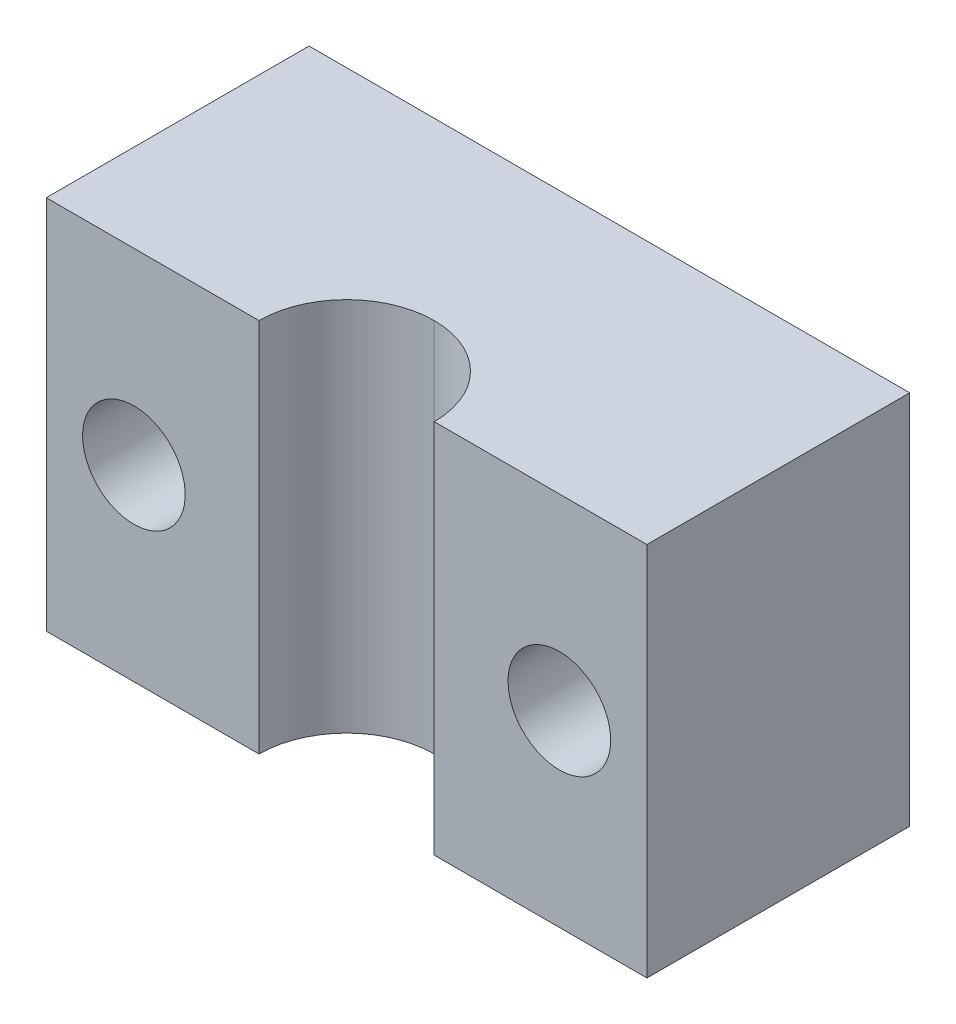
SolidWorks part; units mm, degrees
ref_plane "Спереди" through (0, 0, 0) normal (0, 0, 1) x (1, 0, 0)
ref_plane "Сверху" through (0, 0, 0) normal (0, 1, 0) x (1, 0, 0)
ref_plane "Справа" through (0, 0, 0) normal (1, 0, 0) x (0, 0, -1)
sketch "Эскиз1" plane through (0, 0, 0) normal (0, 1, 0) x (1, 0, 0)
  line L1 (-24, -10) -> (24, -10)
  line L2 (-24, -10) -> (-24, 10)
  line L3 (-24, 10) -> (24, 10)
  line L4 (24, -10) -> (24, 10)
  line L5 (-24, -10) -> (24, 10) construction
  line L6 (-24, 10) -> (24, -10) construction
  point P0 (0, 0)
  dimension "D1" = 48
  dimension "D2" = 20
extrude "Бобышка-Вытянуть1" add sketch "Эскиз1" along normal blind 30
sketch "Эскиз2" plane through (0, 0, 10) normal (0, 0, 1) x (1, 0, 0)
  line L0 (-7, 30) -> (-7, 0)
  line L1 (-24, 30) -> (24, 30) construction
  line L2 (-24, 0) -> (24, 0) construction
  line L3 (-7, 0) -> (7, 0)
  line L4 (7, 0) -> (7, 30)
  line L5 (7, 30) -> (-7, 30)
  dimension "D1" = 17
  dimension "D2" = 14
extrude "Вырез-Вытянуть1" cut sketch "Эскиз2" against normal blind 7
sketch "Эскиз7" plane through (24, 0, 0) normal (1, 0, 0) x (0, 0, -1)
  line L1 (32, 30) -> (32, 0)
  line L2 (32, 0) -> (10, 0)
  line L3 (-10, 0) -> (10, 0)
  line L4 (10, 0) -> (10.066, 0.2736)
  line L5 (10, 30) -> (32, 30)
  line L8 (10, 0) -> (10, 30)
  dimension "D3" = 22
extrude "Бобышка-Вытянуть2" add sketch "Эскиз7" against normal blind 48
sketch "Эскиз8" plane through (24, 0, 0) normal (1, 0, 0) x (0, 0, -1)
  line L0 (11, 0) -> (11, 30)
  line L1 (-10, 30) -> (32, 30) construction
  line L2 (11, 30) -> (32, 30)
  line L3 (11, 0) -> (32, 0)
  line L4 (32, 0) -> (32, 30)
  line L5 (-10, 0) -> (32, 0) construction
  point P16 (11, 0)
extrude "Вырез-Вытянуть2" cut sketch "Эскиз8" against normal blind 14
sketch "Эскиз9" plane through (-24, 0, 0) normal (-1, 0, 0) x (0, 0, 1)
  line L0 (-11, 0) -> (-11, 30)
  line L1 (-32, 30) -> (10, 30) construction
  line L2 (-11, 30) -> (-32, 30)
  line L3 (-32, 0) -> (10, 0) construction
  line L4 (-11, 0) -> (-32, 0)
  line L5 (-32, 0) -> (-32, 30)
  point P15 (-11, 0)
extrude "Вырез-Вытянуть3" cut sketch "Эскиз9" against normal blind 14
sketch "Эскиз11" plane through (-10, 0, 0) normal (-1, 0, 0) x (0, 0, 1)
  line L0 (-32, 30) -> (-11, 0) construction
  line L2 (-32, 0) -> (-11, 0) construction
  line L3 (-16.4, 4.9) -> (-16.4, 25.1)
  line L6 (-16.4, 4.9) -> (-26.6, 4.9)
  line L7 (-16.4, 25.1) -> (-26.6, 25.1)
  line L8 (-26.6, 4.9) -> (-26.6, 25.1)
  line L9 (-16.4, 4.9) -> (-26.6, 25.1) construction
  line L10 (-16.4, 25.1) -> (-26.6, 4.9) construction
  point P7 (-21.5, 15)
  point P8 (-21.5, 15)
  dimension "D1" = 20.2
  dimension "D2" = 10.2
extrude "Вырез-Вытянуть4" cut sketch "Эскиз11" against normal through all
sketch "Эскиз13" plane through (0, 0, -11) normal (0, 0, -1) x (-1, 0, 0)
  line L0 (24, 15) -> (10, 15) construction
  line L1 (24, 0) -> (24, 30) construction
  line L2 (10, 0) -> (10, 30) construction
  line L3 (-10, 15) -> (-24, 15) construction
  line L4 (-10, 30) -> (-10, 0) construction
  line L5 (-24, 30) -> (-24, 0) construction
  circle A0 centre (17, 15) radius 4.1
  circle A1 centre (-17, 15) radius 4.1
  dimension "D1" = 8.2
extrude "Вырез-Вытянуть5" cut sketch "Эскиз13" against normal through all
fillet "Скругление1" radius 7 2 edges at (-7, 15, 3) (7, 15, 3)
sketch "Sketch1" plane through (10, 0, 0) normal (1, 0, 0) x (0, 0, -1)
  line L0 (16.4, 25.1) -> (26.6, 4.9) construction
  line L2 (26.6, 4.9) -> (16.4, 4.9)
  line L3 (26.6, 4.9) -> (26.6, 25.1)
  line L4 (26.6, 25.1) -> (16.4, 25.1)
  line L5 (16.4, 4.9) -> (16.4, 25.1)
  line L6 (26.6, 4.9) -> (16.4, 25.1) construction
  line L7 (26.6, 25.1) -> (16.4, 4.9) construction
  point P4 (21.5, 15)
extrude "Boss-Extrude1" add sketch "Sketch1" against normal blind 4
sketch "Sketch2" plane through (0, 30, 0) normal (0, 1, 0) x (1, 0, 0)
  line L0 (-10, 11) -> (10, 32) construction
  line L2 (-10, 32) -> (10, 32)
  line L3 (-10, 32) -> (-10, 11)
  line L4 (-10, 11) -> (10, 11)
  line L5 (10, 32) -> (10, 11)
  line L6 (-10, 32) -> (10, 11) construction
  line L7 (-10, 11) -> (10, 32) construction
  point P4 (0, 21.5)
extrude "Cut-Extrude1" cut sketch "Sketch2" against normal through all
